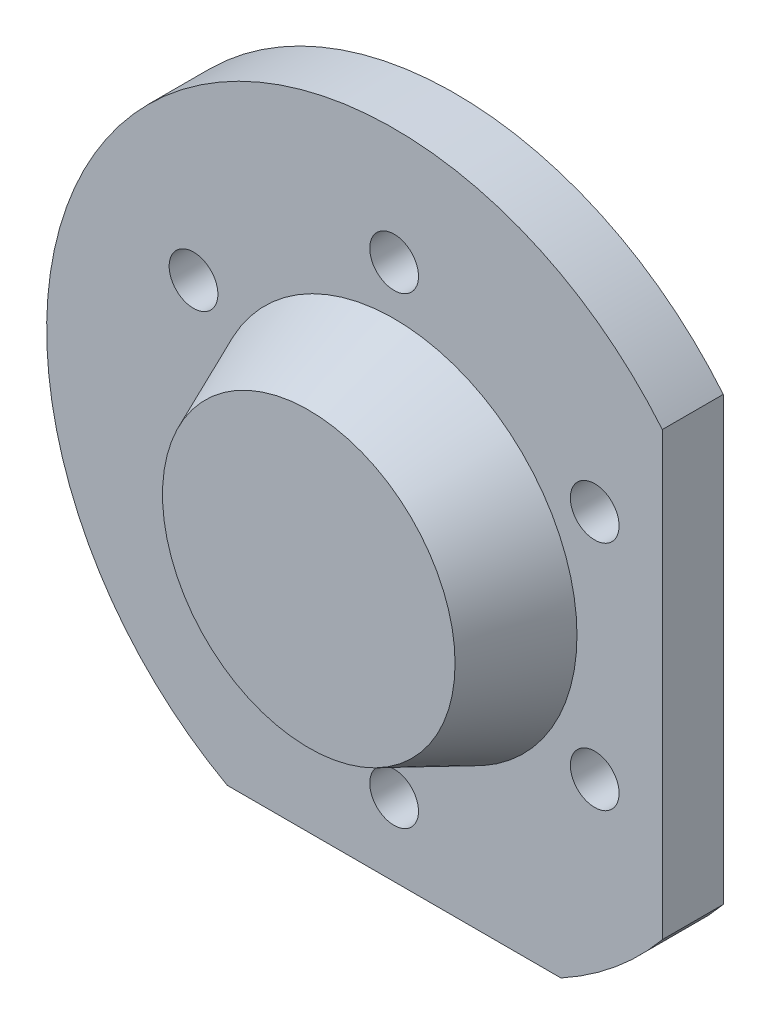
SolidWorks part; units mm, degrees
note: The reader was unsure of these and kept them because the rebuilt part matched: shared geometry of "Sketch1<2>", "Sketch1<4>".
material "Alumina"
ref_plane "Front Plane" through (0, 0, 0) normal (0, 0, 1) x (1, 0, 0)
ref_plane "Top Plane" through (0, 0, 0) normal (0, 1, 0) x (1, 0, 0)
ref_plane "Right Plane" through (0, 0, 0) normal (1, 0, 0) x (0, 0, -1)
sketch "Sketch1" plane through (0, 0, 0) normal (0, 0, 1) x (1, 0, 0)
  line L0 (22, -18.1177) -> (22, 18.1177)
  line L1 (-13.6839, -25) -> (13.6839, -25)
  arc A0 (22, 18.1177) -> (-13.6839, -25) centre (0, 0) ccw
  circle A1 centre (0, 0) radius 15
  circle A2 centre (0, 0) radius 19 construction
  circle A3 centre (0, 19) radius 2
  circle A4 centre (16.4545, 9.5) radius 2
  circle A5 centre (16.4545, -9.5) radius 2
  circle A6 centre (0, -19) radius 2
  circle A7 centre (-16.4545, -9.5) radius 2
  circle A8 centre (-16.4545, 9.5) radius 2
  arc A9 (13.6839, -25) -> (22, -18.1177) centre (0, 0) ccw
  point P19 (0, 0)
  dimension "D1" = 57
  dimension "D2" = 38
  dimension "30" = 30
  dimension "D3" = 4
  dimension "D5" = 22
  dimension "25" = 25
  dimension "D4" = 6
extrude "Boss-Extrude1" add sketch "Sketch1" against normal blind 5
extrude "Boss-Extrude2" add sketch "Sketch1<2>" against normal blind 6 contours A1
sketch "Sketch1<2>" plane through (0, 0, 0) normal (0, 0, 1) x (1, 0, 0) same geometry as "Sketch1"
ref_plane "Plane1" through (0, 0, 7) normal (0, 0, 1) x (1, 0, 0)
sketch "Sketch2" plane through (0, 0, 7) normal (0, 0, 1) x (1, 0, 0)
  circle A0 centre (0, 0) radius 12
  dimension "D1" = 24
loft "Loft1" add profiles "Sketch2" section "Sketch2" section "Sketch1<4>" connector at (11.6342, -2.9404, 7) connector at (14.8504, -2.1135, 0)
sketch "Sketch1<4>" plane through (0, 0, 0) normal (0, 0, 1) x (1, 0, 0) same geometry as "Sketch1"
